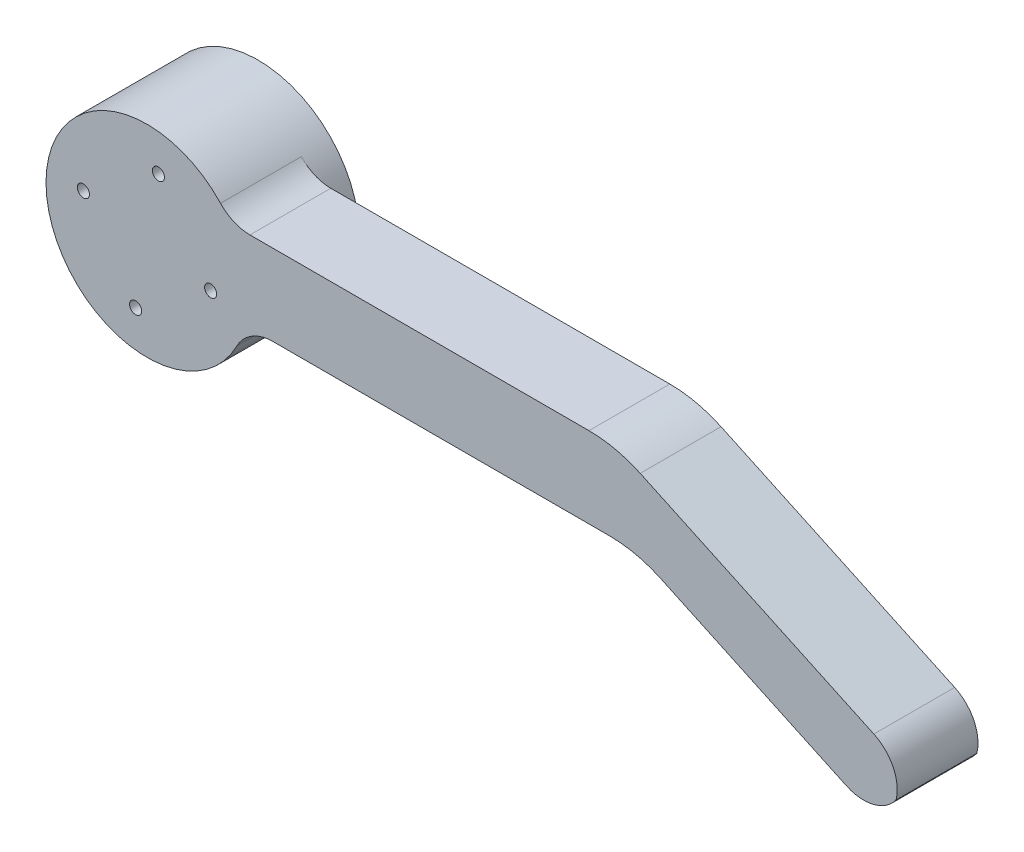
SolidWorks part; units mm, degrees
material "ABS"
ref_plane "Front" through (0, 0, 0) normal (0, 0, 1) x (1, 0, 0)
ref_plane "Top" through (0, 0, 0) normal (0, 1, 0) x (1, 0, 0)
ref_plane "Right" through (0, 0, 0) normal (1, 0, 0) x (0, 0, -1)
sketch "Esquisse1" plane through (0, 0, 0) normal (0, 0, 1) x (1, 0, 0)
  line L2 (10.3562, 7) -> (58.0156, 7)
  line L3 (12.1347, -3) -> (60.5311, -3)
  line L4 (58.0156, 7) -> (94.4722, -10)
  line L5 (94.4722, -10) -> (91.0913, -17.2505)
  line L6 (91.0913, -17.2505) -> (60.5311, -3)
  arc A0 (10.3562, 7) -> (12.1347, -3) centre (0, 0) ccw
  circle A2 centre (0, 0) radius 95 construction
  dimension "D1" = 12.5
  dimension "D4" = 10
  dimension "D5" = 7
  dimension "D9" = 190
  dimension "D2" = 10
  dimension "D3" = 8
  dimension "D8" = 25
extrude "Boss.-Extru.1" add sketch "Esquisse1" along normal mid plane 10
fillet "Congé4" radius 5 2 edges at (12.1347, -3, 0) (10.3562, 7, 0)
fillet "Congé3" radius 15 2 edges at (60.5311, -3, 0) (58.0156, 7, 0)
sketch "Esquisse10" plane through (0, 0, 0) normal (0, 1, 0) x (1, 0, 0)
  line L0 (0.6976, 9.9756) -> (-0.6976, -9.9756)
  line L1 (-50, 0) -> (50, 0) construction
  line L2 (0.6976, 9.9756) -> (3.79, 9.7594)
  line L3 (3.79, 9.7594) -> (2.3949, -10.1919)
  line L4 (2.3949, -10.1919) -> (-0.6976, -9.9756)
  line L5 (0.6976, 9.9756) -> (0.9138, 13.0681) construction
  dimension "D1" = 86
  dimension "D2" = 20
  dimension "D3" = 6.2
revolve "Enlèvement de matière-Révolution1" [suppressed] cut sketch "Esquisse10" angle 360 about L5
sketch "Esquisse13" plane through (0, 0, 0) normal (0, 0, 1) x (1, 0, 0)
  line L0 (1.9, -9) -> (1.9, -12.5)
  line L1 (0, 12.5) -> (3, 12.5)
  line L2 (0, 12.5) -> (0, -12.5)
  line L3 (0, -12.5) -> (1.9, -12.5)
  line L4 (3, 12.5) -> (3, 9.5)
  line L5 (1.9, -9) -> (1.55, -9)
  line L7 (3, 9.5) -> (1.55, 9.5)
  line L8 (1.55, -9) -> (1.55, 9.5)
  line L9 (0, 12.5) -> (0, 15.5) construction
  arc A0 (9.0984, 8.5714) -> (11.1174, -5.7143) centre (0, 0) ccw construction
  dimension "D1" = 6
  dimension "D2" = 3.8
  dimension "D3" = 3.1
  dimension "D4" = 3.5
  dimension "D5" = 3
revolve "Enlèvement de matière-Révolution5" [suppressed] cut sketch "Esquisse13" angle 360 about L9
sketch "Esquisse7" plane through (0, 0, 5) normal (0, 0, 1) x (1, 0, 0)
  circle A0 centre (0, 0) radius 12.5
  arc A2 (9.0984, 8.5714) -> (11.1174, -5.7143) centre (0, 0) ccw construction
extrude "Boss.-Extru.2" [suppressed] add sketch "Esquisse7" against normal blind 0.2
fillet "Congé5" [suppressed] radius 5
sketch "Esquisse8" plane through (0, 0, -5) normal (0, 0, -1) x (-1, 0, 0)
  line L0 (-20.7144, 0.95) -> (-20.7144, -0.15)
  line L3 (-54.6902, 7) -> (-12.7377, 7) construction
  line L4 (-15.5644, -3) -> (-57.2056, -3) construction
  line L5 (-23.5644, -3) -> (-15.5644, -3)
  line L6 (-18.4144, -0.15) -> (-18.4144, 0.95)
  line L8 (-23.5644, 5) -> (-15.5644, 5)
  line L9 (-15.5644, 5) -> (-15.5644, -1)
  line L10 (-16.4144, -0.15) -> (-16.4144, 0.95)
  line L11 (-22.7144, 0.95) -> (-22.7144, -0.15)
  line L12 (-23.5644, -1) -> (-31.5644, -1)
  line L13 (-31.5644, -1) -> (-31.5644, 5)
  line L14 (-30.7144, 4.15) -> (-30.7144, 3.05)
  line L15 (-24.4144, 3.05) -> (-24.4144, 4.15)
  line L16 (-31.5644, 7) -> (-23.5644, 7)
  line L17 (-28.7144, 4.15) -> (-28.7144, 3.05)
  line L18 (-26.4144, 3.05) -> (-26.4144, 4.15)
  arc A2 (-20.7144, -0.15) -> (-23.5644, -3) centre (-23.5644, -0.15) cw
  arc A3 (-15.5644, -3) -> (-18.4144, -0.15) centre (-15.5644, -0.15) cw
  arc A4 (-18.4144, 0.95) -> (-20.7144, 0.95) centre (-19.5644, 0.95) ccw
  arc A5 (-15.5644, -1) -> (-16.4144, -0.15) centre (-15.5644, -0.15) cw
  arc A6 (-16.4144, 0.95) -> (-22.7144, 0.95) centre (-19.5644, 0.95) ccw
  arc A7 (-22.7144, -0.15) -> (-23.5644, -1) centre (-23.5644, -0.15) cw
  arc A8 (-31.5644, 5) -> (-30.7144, 4.15) centre (-31.5644, 4.15) cw
  arc A9 (-30.7144, 3.05) -> (-24.4144, 3.05) centre (-27.5644, 3.05) ccw
  arc A10 (-24.4144, 4.15) -> (-23.5644, 5) centre (-23.5644, 4.15) cw
  arc A11 (-31.5644, 7) -> (-28.7144, 4.15) centre (-31.5644, 4.15) cw
  arc A12 (-28.7144, 3.05) -> (-26.4144, 3.05) centre (-27.5644, 3.05) ccw
  arc A13 (-26.4144, 4.15) -> (-23.5644, 7) centre (-23.5644, 4.15) cw
  dimension "D1" = 2.3
  dimension "D2" = 2
  dimension "D3" = 2
  dimension "D4" = 8
  dimension "D5" = 0.9
  dimension "D6" = 39.1258
  dimension "D7" = 16
  dimension "D9" = 1.7
extrude "Enlèv. mat.-Extru.5" [suppressed] cut sketch "Esquisse8" against normal through all and the other way through all
pattern_linear "Répétition linéaire1" [suppressed] count 3 spacing 16 of bodies 113
fillet "Congé6" radius 5 2 edges at (94.4722, -10, 0) (91.0913, -17.2505, 0) tangent propagation no
sketch "Esquisse15" plane through (0, 0, 0) normal (0, 1, 0) x (1, 0, 0)
  line L0 (0, 5) -> (0, -5) construction
  line L1 (150, 5) -> (8.5, 5)
  line L2 (150, 5) -> (150, 1)
  line L3 (150, 1) -> (50, 1)
  line L5 (-12.5, -5) -> (11.1174, -5) construction
  line L6 (11.1174, 5) -> (-12.5, 5) construction
  line L7 (89.9407, -5) -> (61.0295, -5) construction
  ellipse E0 centre (50, 5) end of major axis (8.5, 5) minor radius 4 (8.5, 5) -> (50, 1) ccw
  dimension "D1" = 6
  dimension "D2" = 17
  dimension "D3" = 50
  dimension "D4" = 150
revolve "Enlèvement de matière-Révolution6" [suppressed] cut sketch "Esquisse15" angle 360 about L0
fillet "Congé7" [suppressed] radius 1
sketch "Sketch1" [suppressed] plane through (0, 0, 0) normal (0, 0, 1) x (1, 0, 0)
  circle A0 centre (0, 0) radius 10.375
  dimension "D1" = 20.75
extrude "Cut-Extrude2" [suppressed] cut sketch "Sketch1" against normal through all from offset 4 offset against normal yes
sketch "Sketch2" [suppressed] plane through (0, 0, 0) normal (1, 0, 0) x (0, 0, -1)
  line L1 (3.8113, -10.375) -> (6.8474, -10.375)
  line L2 (3.8113, -10.375) -> (3.8113, 13.3524)
  line L3 (3.8113, 13.3524) -> (6.8474, 13.3524)
  line L4 (6.8474, -10.375) -> (6.8474, 13.3524)
extrude "Cut-Extrude3" [suppressed] cut sketch "Sketch2" against normal through all and the other way blind 10
sketch "Sketch3" [suppressed] plane through (0, 0, -3.8113) normal (0, 0, -1) x (-1, 0, 0)
  circle A0 centre (-5.7385, -6.5818) radius 0.75
  circle A1 centre (-7.2335, -3.4171) radius 0.75
  circle A2 centre (-8.7285, -0.2525) radius 0.75
  circle A3 centre (-6.5818, 5.7385) radius 0.75
  circle A4 centre (-3.4171, 7.2335) radius 0.75
  circle A5 centre (-0.2525, 8.7285) radius 0.75
  circle A6 centre (0.2525, -8.7285) radius 0.75
  circle A7 centre (3.4171, -7.2335) radius 0.75
  circle A8 centre (6.5818, -5.7385) radius 0.75
  circle A9 centre (8.7285, 0.2525) radius 0.75
  circle A10 centre (7.2335, 3.4171) radius 0.75
  circle A11 centre (5.7385, 6.5818) radius 0.75
extrude "Cut-Extrude4" [suppressed] cut sketch "Sketch3" against normal through all
sketch "Sketch4" plane through (0, 0, -5) normal (0, 0, -1) x (-1, 0, 0)
  circle A0 centre (-1.4105, 7.8747) radius 0.75
  circle A1 centre (7.8747, 1.4105) radius 0.75
  circle A2 centre (1.4105, -7.8747) radius 0.75
  circle A3 centre (-7.8747, -1.4105) radius 0.75
  dimension "D1" = 1.5
  dimension "D2" = 4
extrude "Cut-Extrude5" cut sketch "Sketch4" against normal through all
sketch "Sketch5" plane through (0, 0, -5) normal (0, 0, -1) x (-1, 0, 0)
  circle A0 centre (0, 0) radius 10.5
  circle A1 centre (0, 0) radius 12.5
  dimension "D1" = 21
extrude "Boss-Extrude1" add sketch "Sketch5" along normal blind 3.75
equation "\"D3@Répétition linéaire1\"=\"D7@Esquisse8\""
